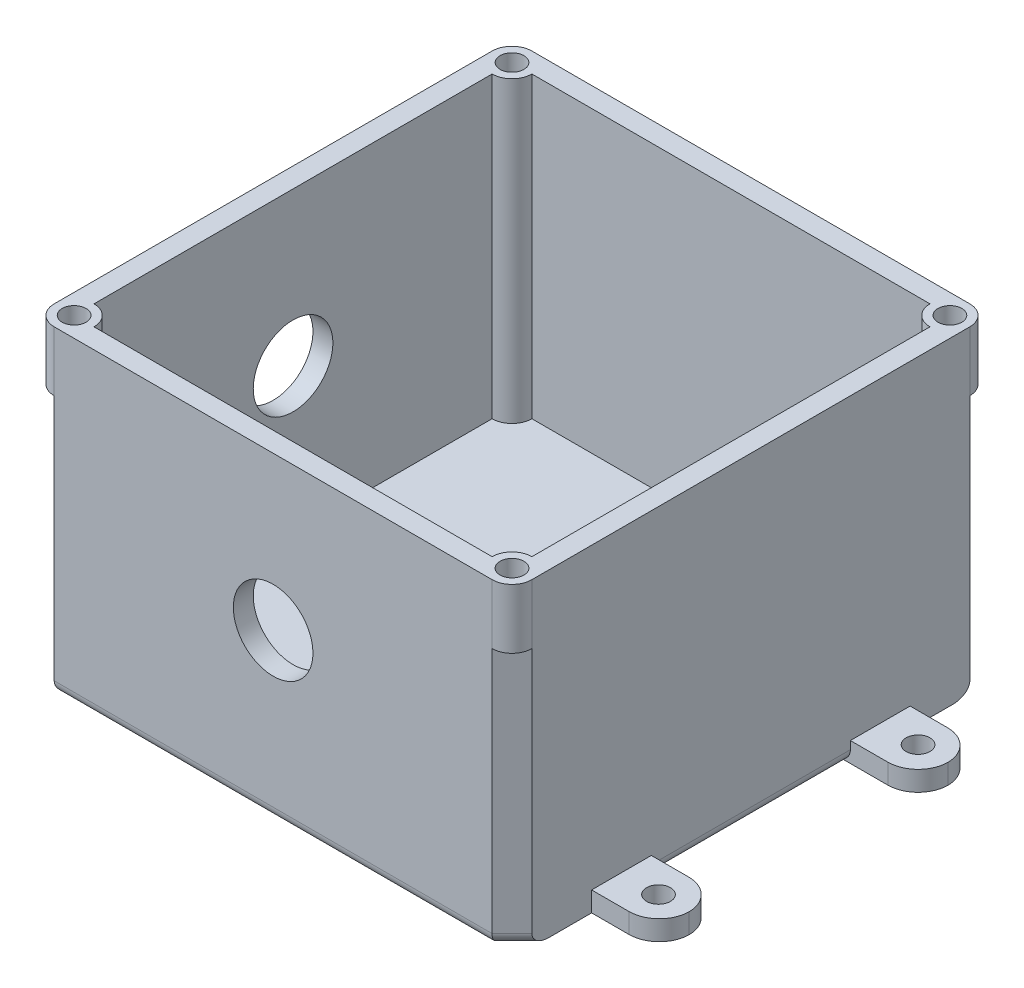
SolidWorks part; units mm, degrees
ref_plane "Front Plane" through (0, 0, 0) normal (0, 0, 1) x (1, 0, 0)
ref_plane "Top Plane" through (0, 0, 0) normal (0, 1, 0) x (1, 0, 0)
ref_plane "Right Plane" through (0, 0, 0) normal (1, 0, 0) x (0, 0, -1)
sketch "Sketch1" plane through (0, 0, 0) normal (0, 1, 0) x (1, 0, 0)
  line L1 (-74.0653, 52.7181) -> (78.3347, 52.7181)
  line L2 (-74.0653, 52.7181) -> (-74.0653, -99.6819)
  line L3 (-74.0653, -99.6819) -> (78.3347, -99.6819)
  line L4 (78.3347, 52.7181) -> (78.3347, -99.6819)
  dimension "D1" = 152.4
  dimension "D2" = 152.4
extrude "Boss-Extrude1" add sketch "Sketch1" along normal blind 101.6
sketch "Sketch2" plane through (0, 0, 0) normal (0, 1, 0) x (1, 0, 0)
  line L0 (78.3347, -99.6819) -> (78.3347, 52.7181) construction
  line L1 (74.5247, -55.2319) -> (99.9247, -55.2319)
  line L2 (74.5247, -55.2319) -> (74.5247, -74.2819)
  line L3 (74.5247, -74.2819) -> (99.9247, -74.2819)
  line L4 (99.9247, -55.2319) -> (99.9247, -74.2819)
  line L5 (-74.0653, -99.6819) -> (78.3347, -99.6819) construction
  line L6 (78.3347, 52.7181) -> (-74.0653, 52.7181) construction
  line L7 (2.1347, 52.7181) -> (2.1347, -99.6819) construction
  line L8 (-70.2553, -74.2819) -> (-95.6553, -74.2819)
  line L9 (-95.6553, -55.2319) -> (-95.6553, -74.2819)
  line L10 (-70.2553, -55.2319) -> (-95.6553, -55.2319)
  line L11 (-70.2553, -55.2319) -> (-70.2553, -74.2819)
  line L12 (-74.0653, -23.4819) -> (78.3347, -23.4819) construction
  line L13 (-74.0653, 52.7181) -> (-74.0653, -99.6819) construction
  line L14 (74.5247, 27.3181) -> (99.9247, 27.3181)
  line L15 (99.9247, 8.2681) -> (99.9247, 27.3181)
  line L16 (74.5247, 8.2681) -> (99.9247, 8.2681)
  line L17 (74.5247, 8.2681) -> (74.5247, 27.3181)
  line L18 (-70.2553, 8.2681) -> (-70.2553, 27.3181)
  line L19 (-70.2553, 8.2681) -> (-95.6553, 8.2681)
  line L20 (-95.6553, 8.2681) -> (-95.6553, 27.3181)
  line L21 (-70.2553, 27.3181) -> (-95.6553, 27.3181)
  dimension "D1" = 19.05
  dimension "D2" = 25.4
  dimension "D3" = 3.81
  dimension "D4" = 25.4
extrude "Boss-Extrude2" add sketch "Sketch2" along normal blind 6.35
sketch "Sketch3" plane through (0, 101.6, 0) normal (0, 1, 0) x (1, 0, 0)
  line L0 (-74.0653, 52.7181) -> (-74.0653, -99.6819) construction
  line L1 (-67.7153, 46.3681) -> (71.9847, 46.3681)
  line L2 (-67.7153, 46.3681) -> (-67.7153, -93.3319)
  line L3 (-67.7153, -93.3319) -> (71.9847, -93.3319)
  line L4 (71.9847, 46.3681) -> (71.9847, -93.3319)
  line L6 (78.3347, 52.7181) -> (-74.0653, 52.7181) construction
  dimension "D1" = 139.7
  dimension "D2" = 139.7
  dimension "D3" = 6.35
  dimension "D4" = 6.35
extrude "Cut-Extrude1" cut sketch "Sketch3" against normal blind 95.25
fillet "Fillet1" radius 9.652 8 edges at (-95.6553, 3.175, -27.3181) (-95.6553, 3.175, -8.2681) (-95.6553, 3.175, 55.2319) (-95.6553, 3.175, 74.2819) (99.9247, 3.175, -27.3181) (99.9247, 3.175, -8.2681) (99.9247, 3.175, 55.2319) (99.9247, 3.175, 74.2819)
chamfer "Chamfer1" distance 6.35 angle 45 4 edges at (78.3347, 50.8, -52.7181) (78.3347, 50.8, 99.6819) (-74.0653, 50.8, -52.7181) (-74.0653, 50.8, 99.6819)
sketch "Sketch4" plane through (0, 6.35, 0) normal (0, 1, 0) x (1, 0, 0)
  line L0 (2.1347, 46.3681) -> (2.1347, -93.3319) construction
  line L1 (71.9847, 46.3681) -> (-67.7153, 46.3681) construction
  line L2 (-67.7153, -93.3319) -> (71.9847, -93.3319) construction
  line L3 (-67.7153, -23.4819) -> (71.9847, -23.4819) construction
  line L4 (-67.7153, 46.3681) -> (-67.7153, -93.3319) construction
  line L5 (71.9847, -93.3319) -> (71.9847, 46.3681) construction
  circle A0 centre (90.2727, -64.8839) radius 3.81
  circle A1 centre (-86.0033, -64.8839) radius 3.81
  circle A2 centre (90.2727, 17.9201) radius 3.81
  circle A3 centre (-86.0033, 17.9201) radius 3.81
extrude "Cut-Extrude2" cut sketch "Sketch4" against normal through all
fillet "Fillet2" radius 3.81 8 edges at (-70.8903, 0, 96.5069) (-74.0653, 0, 23.4819) (-70.8903, 0, -49.5431) (2.1347, 0, -52.7181) (75.1597, 0, -49.5431) (78.3347, 0, 23.4819) (75.1597, 0, 96.5069) (2.1347, 0, 99.6819)
sketch "Sketch5" plane through (0, 101.6, 0) normal (0, 1, 0) x (1, 0, 0)
  line L0 (2.1347, 46.3681) -> (2.1347, -95.6143) construction
  line L1 (71.9847, 46.3681) -> (-67.7153, 46.3681) construction
  line L2 (-67.7153, -23.4819) -> (71.9847, -23.4819) construction
  line L3 (-67.7153, 46.3681) -> (-67.7153, -93.3319) construction
  line L4 (71.9847, -93.3319) -> (71.9847, 46.3681) construction
  circle A1 centre (71.9847, -93.3319) radius 6.35
  circle A4 centre (-67.7153, -93.3319) radius 6.35
  circle A5 centre (-67.7153, 46.3681) radius 6.35
  circle A8 centre (71.9847, 46.3681) radius 6.35
extrude "Boss-Extrude3" add sketch "Sketch5" against normal blind 19.05
sketch "Sketch6" plane through (0, 101.6, 0) normal (0, 1, 0) x (1, 0, 0)
  line L0 (2.1347, 46.3681) -> (2.1347, -96.2606) construction
  line L2 (71.9847, 46.3681) -> (-67.7153, 46.3681) construction
  line L3 (-67.7153, -23.4819) -> (71.9847, -23.4819) construction
  line L4 (-67.7153, 46.3681) -> (-67.7153, -93.3319) construction
  line L5 (71.9847, -86.9819) -> (71.9847, 40.0181) construction
  circle A0 centre (71.9847, -93.3319) radius 3.81
  circle A1 centre (-67.7153, -93.3319) radius 3.81
  circle A2 centre (71.9847, 46.3681) radius 3.81
  circle A3 centre (-67.7153, 46.3681) radius 3.81
sketch "Sketch7" plane through (0, 101.6, 0) normal (0, 1, 0) x (1, 0, 0)
  line L0 (71.9847, -99.6819) -> (78.3347, -93.3319)
  line L1 (2.1347, 39.6749) -> (2.1347, -77.7516) construction
  line L2 (2.1347, 46.3681) -> (2.1347, -96.2606) construction
  line L3 (-67.7153, -23.4819) -> (71.9847, -23.4819) construction
  line L4 (-51.527, -23.4819) -> (55.8667, -23.4819) construction
  line L5 (-67.7153, -99.6819) -> (-74.0653, -93.3319)
  line L6 (71.9847, 52.7181) -> (78.3347, 46.3681)
  line L7 (-67.7153, 52.7181) -> (-74.0653, 46.3681)
  arc A0 (78.3347, -93.3319) -> (71.9847, -99.6819) centre (71.9847, -93.3319) ccw
  arc A1 (-74.0653, -93.3319) -> (-67.7153, -99.6819) centre (-67.7153, -93.3319) cw
  arc A3 (78.3347, 46.3681) -> (71.9847, 52.7181) centre (71.9847, 46.3681) cw
  arc A4 (-74.0653, 46.3681) -> (-67.7153, 52.7181) centre (-67.7153, 46.3681) ccw
extrude "Boss-Extrude4" add sketch "Sketch7" against normal blind 95.25
extrude "Cut-Extrude3" cut sketch "Sketch6" against normal blind 17.272
sketch "Sketch8" plane through (0, 0, 99.6819) normal (0, 0, 1) x (1, 0, 0)
  line L0 (2.1347, 101.6) -> (2.1347, 0) construction
  line L1 (-67.7153, 101.6) -> (71.9847, 101.6) construction
  line L2 (-67.7153, 101.6) -> (-67.7153, 3.81) construction
  line L3 (-67.7153, 52.705) -> (71.9847, 52.705) construction
  line L4 (71.9847, 3.81) -> (71.9847, 82.55) construction
  circle A0 centre (2.1347, 52.705) radius 12.7
extrude "Cut-Extrude4" cut sketch "Sketch8" against normal up to next
sketch "Sketch9" plane through (-74.0653, 0, 0) normal (-1, 0, 0) x (0, 0, 1)
  line L0 (-46.3681, 101.6) -> (-46.3681, 3.81) construction
  line L1 (23.4819, 101.6) -> (23.4819, 3.81) construction
  line L2 (-46.3681, 101.6) -> (93.3319, 101.6) construction
  line L3 (-8.2681, 3.81) -> (55.2319, 3.81) construction
  line L4 (-46.3681, 52.705) -> (94.078, 52.705) construction
  circle A0 centre (23.4819, 52.705) radius 12.7
extrude "Cut-Extrude5" cut sketch "Sketch9" against normal up to next
